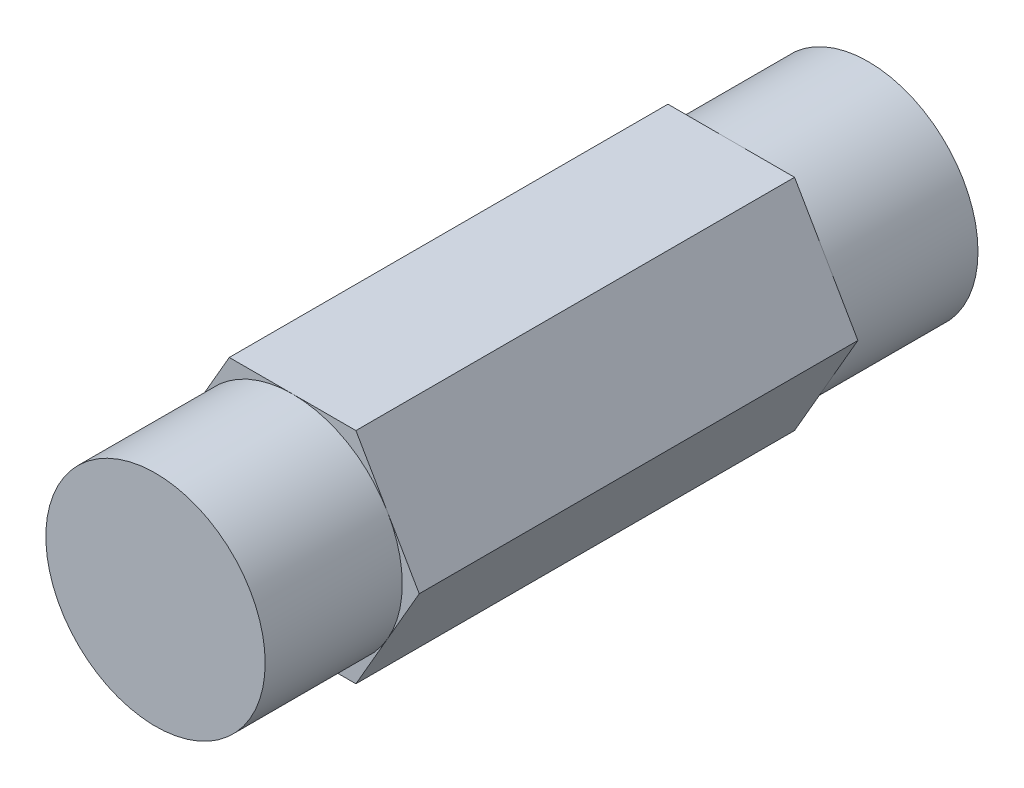
SolidWorks part; units mm, degrees
ref_plane "Front Plane" through (0, 0, 0) normal (0, 0, 1) x (1, 0, 0)
ref_plane "Top Plane" through (0, 0, 0) normal (0, 1, 0) x (1, 0, 0)
ref_plane "Right Plane" through (0, 0, 0) normal (1, 0, 0) x (0, 0, -1)
sketch "Sketch1" plane through (0, 0, 0) normal (0, 0, 1) x (1, 0, 0)
  line L1 (3.6662, 6.35) -> (-3.6662, 6.35)
  line L2 (-3.6662, 6.35) -> (-7.3323, 0)
  line L3 (-7.3323, 0) -> (-3.6662, -6.35)
  line L4 (-3.6662, -6.35) -> (3.6662, -6.35)
  line L5 (3.6662, -6.35) -> (7.3323, 0)
  line L6 (7.3323, 0) -> (3.6662, 6.35)
  circle A0 centre (0, 0) radius 6.35 construction
  point P1 (0, 6.35)
  dimension "D1" = 12.7
extrude "Boss-Extrude1" add sketch "Sketch1" along normal mid plane 41.275
sketch "Sketch2" plane through (0, 0, 20.6375) normal (0, 0, 1) x (1, 0, 0)
  circle A0 centre (0, 0) radius 6.35
  dimension "D1" = 12.7
extrude "Cut-Extrude4" cut sketch "Sketch2" against normal blind 7.9375 flip side to cut contours A0 region at (0, 0, 20.6375)
mirror "Mirror1" about plane through (0, 0, 0) normal (0, 0, 1) of "Cut-Extrude4"
